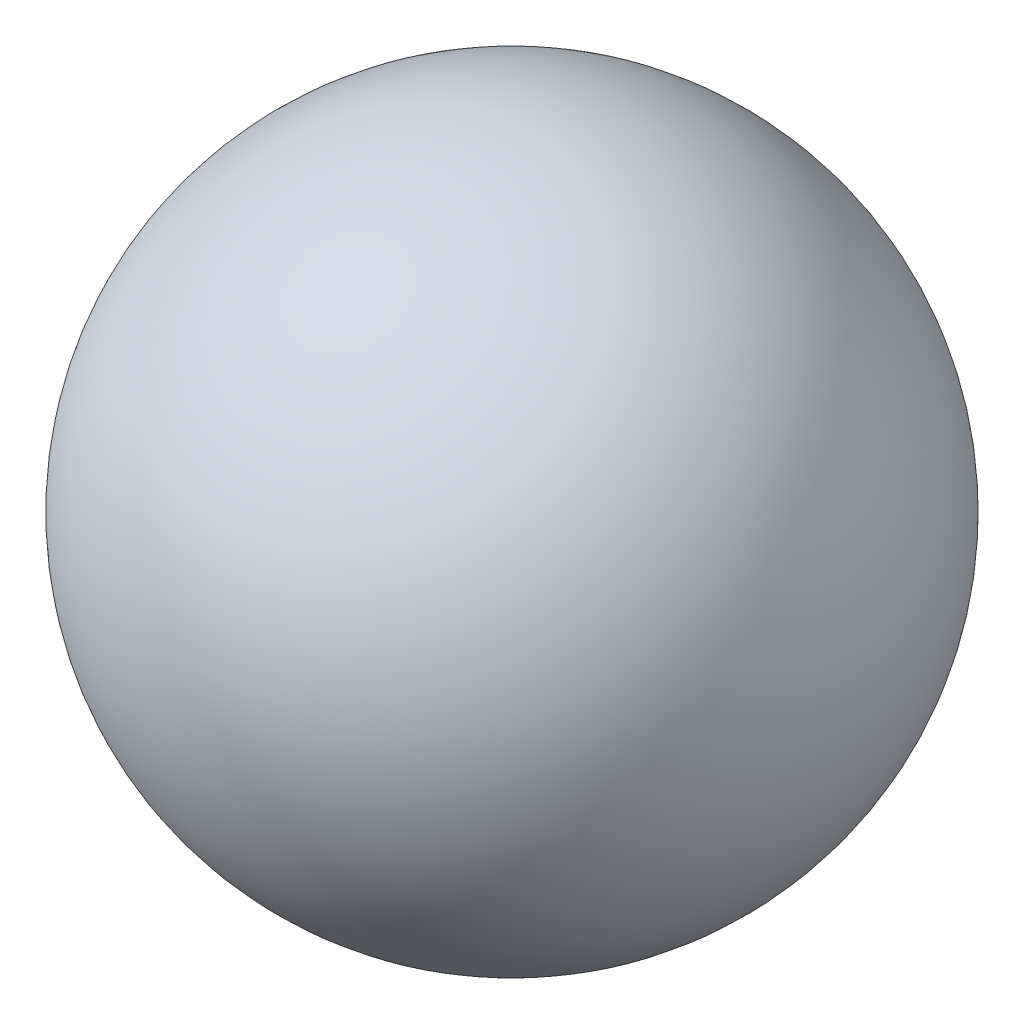
SolidWorks part; units mm, degrees
ref_plane "Front Plane" through (0, 0, 0) normal (0, 0, 1) x (1, 0, 0)
ref_plane "Top Plane" through (0, 0, 0) normal (0, 1, 0) x (1, 0, 0)
ref_plane "Right Plane" through (0, 0, 0) normal (1, 0, 0) x (0, 0, -1)
sketch "Sketch1" plane through (0, 0, 0) normal (0, 0, 1) x (1, 0, 0)
  line L0 (0, -21.5) -> (0, 21.5)
  arc A0 (0, 21.5) -> (0, -21.5) centre (0, 0) cw
  dimension "D1" = 21.5
revolve "Revolve1" add sketch "Sketch1" angle 360 about L0
sketch "Sketch2" plane through (0, 0, 0) normal (0, 0, 1) x (1, 0, 0)
  line L0 (-23.9076, 0) -> (23.9076, 0)
ref_plane "Plane1" through (0, 0, 0) normal (0, 0.7071, 0.7071) x (1, 0, 0)
sketch "Sketch3" plane through (0, 0, 0) normal (0, 0.7071, 0.7071) x (1, 0, 0)
  line L0 (-23.9076, 0) -> (23.9076, 0) construction
  line L1 (-21.5, 0) -> (-21.5, 9.747)
  arc A0 (-21.5, 0) -> (21.5, 0) centre (0, 0) cw
  circle A1 centre (0, 0) radius 21.5 construction
sketch "Sketch4" plane through (0, 0, 0) normal (0, 0.7071, 0.7071) x (1, 0, 0)
  line L0 (0, 0) -> (15.2028, 15.2028)
  line L1 (15.2028, 15.2028) -> (0, 0)
  line L2 (-15.2028, 15.2028) -> (0, 0)
  line L3 (-23.9076, 0) -> (23.9076, 0) construction
  arc A0 (21.5, 0) -> (-21.5, 0) centre (0, 0) ccw construction
  dimension "D1" = 45
  dimension "D2" = 45
ref_plane "Plane2" through (0, 0, 0) normal (0.7071, -0.5, 0.5) x (0.7071, 0.5, -0.5)
ref_plane "Plane3" through (0, 0, 0) normal (-0.7071, -0.5, 0.5) x (0.7071, -0.5, 0.5)
